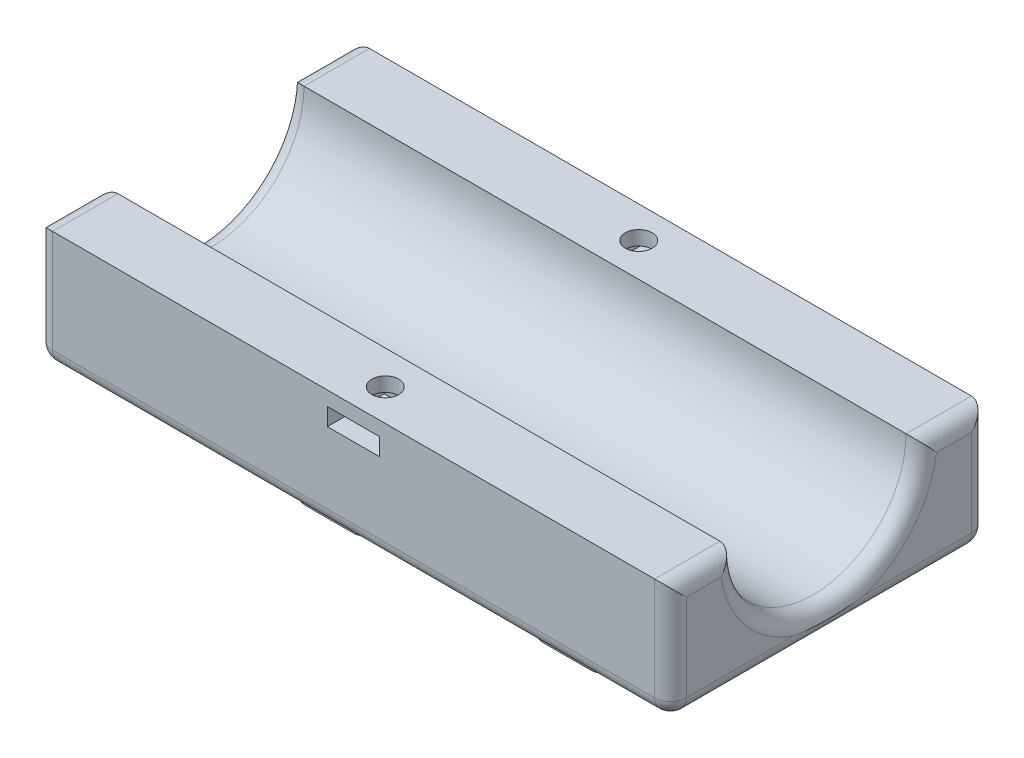
SolidWorks part; units mm, degrees
ref_plane "Front Plane" through (0, 0, 0) normal (0, 0, 1) x (1, 0, 0)
ref_plane "Top Plane" through (0, 0, 0) normal (0, 1, 0) x (1, 0, 0)
ref_plane "Right Plane" through (0, 0, 0) normal (1, 0, 0) x (0, 0, -1)
sketch "Sketch3" plane through (0, 0, 0) normal (1, 0, 0) x (0, 0, -1)
  line L0 (40.3225, 19.05) -> (50.8, 19.05)
  line L1 (0, 0) -> (50.8, 0)
  line L2 (0, 0) -> (0, 19.05)
  line L3 (0, 19.05) -> (10.4775, 19.05)
  line L4 (50.8, 0) -> (50.8, 19.05)
  arc A0 (10.4775, 19.05) -> (40.3225, 19.05) centre (25.4, 19.05) ccw
  point P9 (25.4, 0)
  dimension "D1" = 14.9225
  dimension "D2" = 50.8
  dimension "D3" = 19.05
extrude "Boss-Extrude2" add sketch "Sketch3" along normal blind 101.6
ref_plane "Plane3" through (0, 0, -35.56) normal (0, 0, -1) x (-1, 0, 0)
sketch "Sketch14" plane through (0, 0, -35.56) normal (0, 0, -1) x (-1, 0, 0)
  line L0 (-101.6, 0) -> (0, 0) construction
  line L1 (-63.5, 0) -> (-76.2, 0)
  line L2 (-63.5, 0) -> (-63.5, -13.97)
  line L3 (-63.5, -13.97) -> (-76.2, -13.97)
  line L4 (-76.2, 0) -> (-76.2, -13.97)
  line L5 (-69.85, -5.08) -> (-69.85, -8.89) construction
  line L6 (-25.4, 0) -> (-38.1, 0)
  line L7 (-25.4, 0) -> (-25.4, -13.97)
  line L8 (-25.4, -13.97) -> (-38.1, -13.97)
  line L9 (-38.1, 0) -> (-38.1, -13.97)
  line L10 (-66.675, -5.08) -> (-66.675, -8.89)
  line L11 (-73.025, -5.08) -> (-73.025, -8.89)
  line L12 (-31.75, -5.08) -> (-31.75, -8.89) construction
  line L13 (-28.575, -5.08) -> (-28.575, -8.89)
  line L14 (-34.925, -5.08) -> (-34.925, -8.89)
  arc A0 (-66.675, -5.08) -> (-73.025, -5.08) centre (-69.85, -5.08) ccw
  arc A1 (-73.025, -8.89) -> (-66.675, -8.89) centre (-69.85, -8.89) ccw
  arc A2 (-28.575, -5.08) -> (-34.925, -5.08) centre (-31.75, -5.08) ccw
  arc A3 (-34.925, -8.89) -> (-28.575, -8.89) centre (-31.75, -8.89) ccw
  point P10 (-69.85, -13.97)
  point P11 (-31.75, -13.97)
  point P14 (-69.85, -6.985)
  point P16 (-50.8, 0)
  point P20 (-31.75, -6.985)
  point P27 (-28.575, -6.985)
  point P28 (-31.8272, -4.2479)
  point P29 (-69.6647, -1.3979)
  point P30 (0, 0)
  point P32 (0, 0)
  point P33 (0, 0)
  point P34 (0, 0)
  dimension "D5" = 6.35
  dimension "D1" = 38.1
  dimension "D2" = 19.05
  dimension "D3" = 12.7
  dimension "D4" = 13.97
  dimension "D6" = 3.81
  dimension "D7" = 5.08
extrude "Boss-Extrude3" add sketch "Sketch14" against normal blind 20.32
hole_wizard "#6 Clearance Hole1" positions "Sketch5" profile "Sketch6" hole size "#6" standard "ANSI Inch" end condition through all
sketch "Sketch5" plane through (0, 19.05, 0) normal (0, 1, 0) x (1, 0, 0)
  line L0 (101.6, 0) -> (0, 0) construction
  line L1 (0, 25.4) -> (101.6, 25.4) construction
  line L2 (0, 40.3225) -> (0, 10.4775) construction
  line L3 (101.6, 10.4775) -> (101.6, 40.3225) construction
  line L4 (50.8, 0) -> (50.8, 50.8) construction
  line L5 (101.6, 50.8) -> (0, 50.8) construction
  point P0 (50.8, 5.08)
  point P2 (50.8, 45.72)
  dimension "D1" = 5.08
sketch "Sketch6" plane through (50.8, 19.05, -5.08) normal (1, 0, 0) x (0, 0, 1)
  line L0 (0, 0) -> (0, 33.02)
  line L1 (0, 33.02) -> (2.1526, 33.02)
  line L2 (2.1526, 33.02) -> (2.1526, 0)
  line L5 (2.1526, 0) -> (0, 0)
  line L11 (0, -6.35) -> (0, 107.95) construction
  dimension "Thru Hole Dia." = 4.3053
  dimension "Thru Hole Depth" = 33.02
ref_plane "Plane1" through (0, 13.97, 0) normal (0, 1, 0) x (1, 0, 0)
sketch "Sketch8" plane through (0, 13.97, 0) normal (0, 1, 0) x (1, 0, 0)
  line L0 (101.6, 0) -> (0, 0) construction
  line L1 (46.609, 9.144) -> (54.991, 9.144)
  line L2 (46.609, 9.144) -> (46.609, 0)
  line L3 (46.609, 0) -> (54.991, 0)
  line L4 (54.991, 9.144) -> (54.991, 0)
  line L5 (101.6, 50.8) -> (0, 50.8) construction
  line L6 (46.609, 41.656) -> (54.991, 41.656)
  line L7 (46.609, 41.656) -> (46.609, 50.8)
  line L8 (46.609, 50.8) -> (54.991, 50.8)
  line L9 (54.991, 41.656) -> (54.991, 50.8)
  circle A0 centre (50.8, 5.08) radius 2.1526 construction
  point P12 (63.4387, 0)
  point P16 (50.8, 0)
  point P17 (50.8, 0)
  dimension "D2" = 4.064
  dimension "D1" = 8.382
extrude "Cut-Extrude2" cut sketch "Sketch8" along normal blind 2.794
hole_wizard "#6 Clearance Hole2" [suppressed] positions "Sketch9" profile "Sketch10" hole size "#6" standard "ANSI Inch"
sketch "Sketch9" plane through (0, 0, 0) normal (0, -1, 0) x (-1, 0, 0)
  line L0 (-101.6, 0) -> (-101.6, 50.8) construction
  line L1 (-101.6, 50.8) -> (0, 50.8) construction
  line L4 (-78.74, 45.72) -> (-22.86, 5.08) construction
  line L5 (-101.6, 0) -> (0, 0) construction
  point P0 (-78.74, 45.72)
  point P2 (-22.86, 5.08)
  point P30 (-50.8, 25.4)
  dimension "D1" = 55.88
  dimension "D2" = 5.08
  dimension "D3" = 50.8
  dimension "D4" = 5.08
sketch "Sketch10" plane through (78.74, 0, -45.72) normal (1, 0, 0) x (0, 0, -1)
  line L0 (0, 0) -> (0, 13.9934)
  line L1 (0, 13.9934) -> (2.1526, 12.7)
  line L2 (2.1526, 12.7) -> (2.1526, 0)
  line L5 (2.1526, 0) -> (0, 0)
  line L10 (0, 13.9934) -> (-2.1527, 12.7) construction
  line L11 (0, -6.35) -> (0, 107.95) construction
  dimension "Hole Dia." = 4.3053
  dimension "Hole Depth" = 12.7
  dimension "Drill Angle" = 118
ref_plane "Plane2" through (0, 7.62, 0) normal (0, -1, 0) x (-1, 0, 0)
sketch "Sketch11" [suppressed] plane through (0, 7.62, 0) normal (0, -1, 0) x (-1, 0, 0)
  line L0 (-101.6, 50.8) -> (0, 50.8) construction
  line L1 (-82.931, 41.656) -> (-74.549, 41.656)
  line L2 (-82.931, 41.656) -> (-82.931, 50.8)
  line L3 (-82.931, 50.8) -> (-74.549, 50.8)
  line L4 (-74.549, 41.656) -> (-74.549, 50.8)
  line L10 (-101.6, 0) -> (0, 0) construction
  line L11 (-27.051, 0) -> (-18.669, 0)
  line L12 (-27.051, 0) -> (-27.051, 9.144)
  line L13 (-27.051, 9.144) -> (-18.669, 9.144)
  line L14 (-18.669, 0) -> (-18.669, 9.144)
  point P24 (-78.74, 41.656)
  point P25 (-22.86, 9.144)
  dimension "D1" = 8.382
  dimension "D2" = 4.064
extrude "Cut-Extrude3" [suppressed] cut sketch "Sketch11" along normal blind 3.302
fillet "Fillet1" radius 2.54 22 edges at (101.6, 4.1275, -25.4) (0, 4.1275, -25.4) (0, 9.525, -50.8) (101.6, 9.525, -50.8) (0, 9.525, 0) (101.6, 9.525, 0) (25.4, 0, -25.4) (25.4, -13.97, -25.4) (38.1, -13.97, -25.4) (38.1, 0, -25.4) (76.2, 0, -25.4) (63.5, 0, -25.4) (63.5, -13.97, -25.4) (76.2, -13.97, -25.4) (50.8, 0, 0) (101.6, 0, -25.4) (50.8, 0, -50.8) (0, 0, -25.4) (101.6, 19.05, -5.2388) (101.6, 19.05, -45.5613) (0, 19.05, -45.5613) (0, 19.05, -5.2388)
